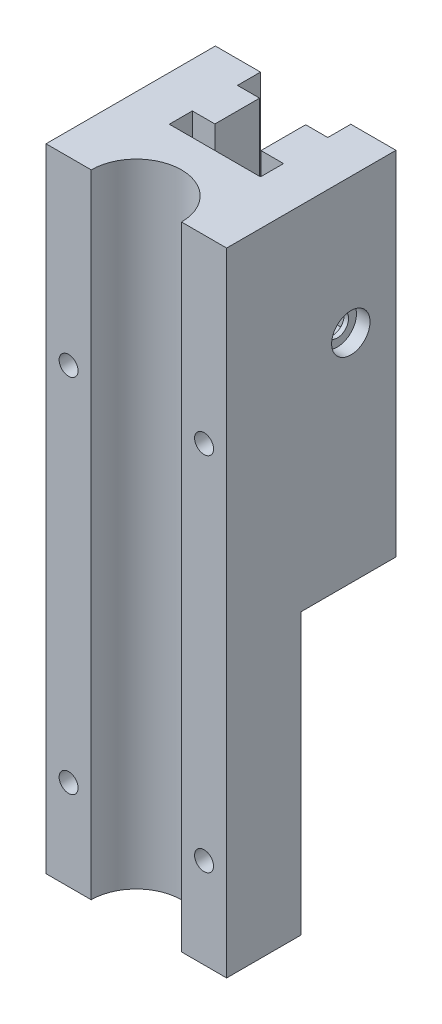
SolidWorks part; units mm, degrees
other "Markup1"
sketch "Sketch9" plane through (-20, 0, 37.5) normal (-0.6467, 0.1839, 0.7403) x (0.76, 0.0728, 0.6458)
ref_plane "Front Plane" through (0, 0, 0) normal (0, 0, 1) x (1, 0, 0)
ref_plane "Top Plane" through (0, 0, 0) normal (0, 1, 0) x (1, 0, 0)
ref_plane "Right Plane" through (0, 0, 0) normal (1, 0, 0) x (0, 0, -1)
sketch "Sketch1" plane through (0, 0, 0) normal (0, 1, 0) x (1, 0, 0)
  line L0 (10, 0) -> (-10, 0) construction
  line L1 (-10, 0) -> (-20, 0)
  line L2 (-20, 0) -> (-20, -37.5)
  line L3 (-20, -37.5) -> (20, -37.5)
  line L4 (20, -37.5) -> (20, 0)
  line L5 (20, 0) -> (10, 0)
  line L6 (10, 0) -> (10, -5.1)
  line L7 (10, -5.1) -> (5.1, -5.1)
  line L8 (5.1, -5.1) -> (5.1, -15)
  line L9 (5.1, -15) -> (10.1, -15)
  line L10 (10.1, -15) -> (10.1, -20.1)
  line L11 (10.1, -20.1) -> (-10.1, -20.1)
  line L12 (0, 0) -> (0, -20.1) construction
  line L13 (-10, 0) -> (-10, -5.1)
  line L14 (-10, -5.1) -> (-5.1, -5.1)
  line L15 (-5.1, -5.1) -> (-5.1, -15)
  line L16 (-5.1, -15) -> (-10.1, -15)
  line L17 (-10.1, -15) -> (-10.1, -20.1)
  line L18 (0, 0) -> (0, -37.5) construction
  circle A1 centre (0, -37.5) radius 10
  point P3 (0, 0)
  dimension "D10" = 20
  dimension "D1" = 37.5
  dimension "D2" = 5.1
  dimension "D3" = 4.9
  dimension "D4" = 5
  dimension "D5" = 9.9
  dimension "D6" = 5.1
  dimension "D7" = 10.1
  dimension "D8" = 40
  dimension "D9" = 20
  dimension "D11" = 37.5
extrude "Boss-Extrude1" add sketch "Sketch1" against normal blind 140 contours A1 L3 L4 L5 L6 L7 L8 L9 L10 L11 L17 L16 L15 L14 L13 L1 L2 region at (-10.5483, 0, 2.55)
sketch "Sketch5" plane through (0, -140, 0) normal (0, -1, 0) x (1, 0, 0)
  line L0 (-20, 0) -> (-20, 37.5) construction
  line L1 (20, 0) -> (-20, 0)
  line L2 (20, 0) -> (20, 21)
  line L3 (20, 21) -> (-20, 21)
  line L4 (-20, 0) -> (-20, 21)
  dimension "D1" = 21
extrude "Cut-Extrude5" cut sketch "Sketch5" against normal blind 62
sketch "Sketch3" plane through (20, 0, 0) normal (1, 0, 0) x (0, 0, -1)
  line L0 (0, -78) -> (0, 0) construction
  line L1 (0, 0) -> (-20, 0)
  line L2 (0, 0) -> (0, -25)
  line L3 (0, -25) -> (-20, -25)
  line L4 (-20, 0) -> (-20, -25)
  line L5 (-20, -25) -> (0, -25)
  line L6 (-20, -25) -> (-20, -35)
  line L7 (-20, -35) -> (0, -35)
  line L8 (0, -25) -> (0, -35)
  line L9 (-15, -25) -> (-15, -35)
  line L10 (-5, -25) -> (-5, -35)
  line L11 (-10, -25) -> (-10, -35) construction
  line L12 (-15, -30) -> (-5, -30) construction
  line L13 (-37.5, 0) -> (0, 0) construction
  circle A0 centre (-10, -30) radius 2.5
  circle A1 centre (-10, -30) radius 4.25
  dimension "D6" = 5
  dimension "D7" = 8.5
  dimension "D1" = 20
  dimension "D2" = 0
  dimension "D3" = 10
  dimension "D4" = 5
  dimension "D5" = 10
  dimension "D9" = 25
extrude "Cut-Extrude2" cut sketch "Sketch3" against normal blind 30 and the other way blind 1 from offset 5 contours L10 L5 L9 L7 | A1 A0 | A0 region at (20, -30, 5.1414) region at (20, -30, 10) region at (20, -30, 14.1298) offset against normal yes
extrude "Cut-Extrude3" cut sketch "Sketch3<3>" against normal through all contours A0 region at (20, -30, 10)
sketch "Sketch3<3>" plane through (20, 0, 0) normal (1, 0, 0) x (0, 0, -1) same geometry as "Sketch3"
extrude "Cut-Extrude4" cut sketch "Sketch3<5>" against normal blind 3 contours A1 A0 region at (20, -30, 14.1298)
sketch "Sketch3<5>" plane through (20, 0, 0) normal (1, 0, 0) x (0, 0, -1) same geometry as "Sketch3"
mirror "Mirror1" about plane through (0, 0, 0) normal (1, 0, 0) of "Cut-Extrude4"
sketch "Sketch7" plane through (0, 0, 37.5) normal (0, 0, 1) x (1, 0, 0)
  line L0 (-20, -140) -> (-10, -140) construction
  line L1 (-10, -140) -> (-10, 0) construction
  line L2 (10, -140) -> (20, -140) construction
  line L3 (10, -140) -> (10, 0) construction
  line L4 (20, -140) -> (20, 0) construction
  line L5 (10, 0) -> (20, 0) construction
  line L6 (-20, 0) -> (-10, 0) construction
  line L7 (-20, -140) -> (-20, 0) construction
  line L8 (-20, -140) -> (-10, -140)
  line L9 (-10, -140) -> (-10, 0)
  line L10 (10, -140) -> (20, -140)
  line L11 (10, -140) -> (10, 0)
  line L12 (20, -140) -> (20, 0)
  line L13 (10, 0) -> (20, 0)
  line L14 (-20, 0) -> (-10, 0)
  line L15 (-20, -140) -> (-20, 0)
  line L16 (0, -140) -> (0, 0) construction
  line L17 (-10, 0) -> (10, 0)
  line L18 (-10, 0) -> (-10, -140)
  line L19 (-10, -140) -> (10, -140)
  line L20 (10, 0) -> (10, -140)
  line L21 (-15, 0) -> (-15, -140) construction
  line L22 (15, 0) -> (15, -140) construction
  circle A0 centre (-15, -120) radius 2.1
  circle A1 centre (15, -120) radius 2.1
  circle A2 centre (-15, -40) radius 2.1
  circle A3 centre (15, -40) radius 2.1
  dimension "D1" = 4.2
  dimension "D2" = 4.2
  dimension "D7" = 4.2
  dimension "D8" = 4.2
  dimension "D3" = 20
  dimension "D4" = 20
  dimension "D5" = 40
  dimension "D6" = 40
extrude "Cut-Extrude7" cut sketch "Sketch7" against normal blind 10 contours A2 | A3 | A1 | A0
